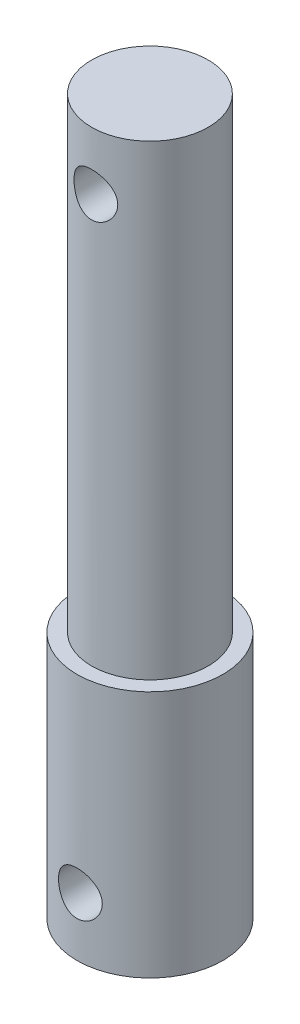
SolidWorks part; units mm, degrees
ref_plane "Front Plane" through (0, 0, 0) normal (0, 0, 1) x (1, 0, 0)
ref_plane "Top Plane" through (0, 0, 0) normal (0, 1, 0) x (1, 0, 0)
ref_plane "Right Plane" through (0, 0, 0) normal (1, 0, 0) x (0, 0, -1)
sketch "Sketch1" plane through (0, 0, 0) normal (0, 1, 0) x (1, 0, 0)
  circle A0 centre (0, 0) radius 5
  circle A1 centre (0, 0) radius 4
  dimension "D1" = 10
  dimension "D2" = 8
extrude "Boss-Extrude1" add sketch "Sketch1" along normal blind 17 contours A1 | A0 A1 region at (-4.8586, 0, 0) region at (0, 0, 0)
extrude "Boss-Extrude2" add sketch "Sketch1<3>" along normal blind 49 contours A1 region at (0, 0, 0)
sketch "Sketch1<3>" plane through (0, 0, 0) normal (0, 1, 0) x (1, 0, 0) same geometry as "Sketch1"
sketch "Sketch2" plane through (0, 0, 0) normal (0, 0, 1) x (1, 0, 0)
  circle A0 centre (0, 45) radius 1.5
  circle A1 centre (0, 4) radius 1.5
extrude "Cut-Extrude1" cut sketch "Sketch2" against normal through all both and the other way through all
